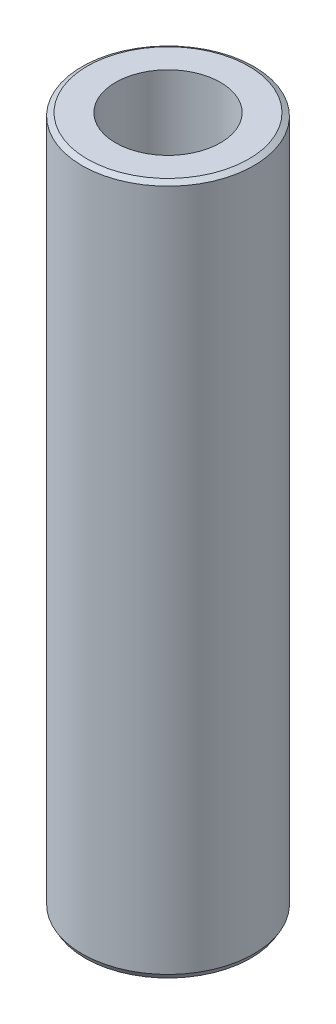
SolidWorks part; units mm, degrees
ref_plane "Front Plane" through (0, 0, 0) normal (0, 0, 1) x (1, 0, 0)
ref_plane "Top Plane" through (0, 0, 0) normal (0, 1, 0) x (1, 0, 0)
ref_plane "Right Plane" through (0, 0, 0) normal (1, 0, 0) x (0, 0, -1)
sketch "Sketch1" plane through (0, 0, 0) normal (0, 1, 0) x (1, 0, 0)
  circle A0 centre (0, 0) radius 22.5
  dimension "SHAFT_OD" = 45
extrude "Boss-Extrude1" add sketch "Sketch1" along normal blind 180.987
sketch "Sketch2" plane through (0, 0, 0) normal (0, 1, 0) x (1, 0, 0)
  circle A0 centre (0, 0) radius 13.7377
  dimension "BORE_D" = 27.4754
extrude "Cut-Extrude1" cut sketch "Sketch2" along normal through all
chamfer "Chamfer1" distance 0.796 angle 60 2 edges at (0, 180.987, 22.5) (0, 0, 22.5) first distance on face at (0, 180.987, 22.5) first distance on face at (0, 0, 13.7377)
